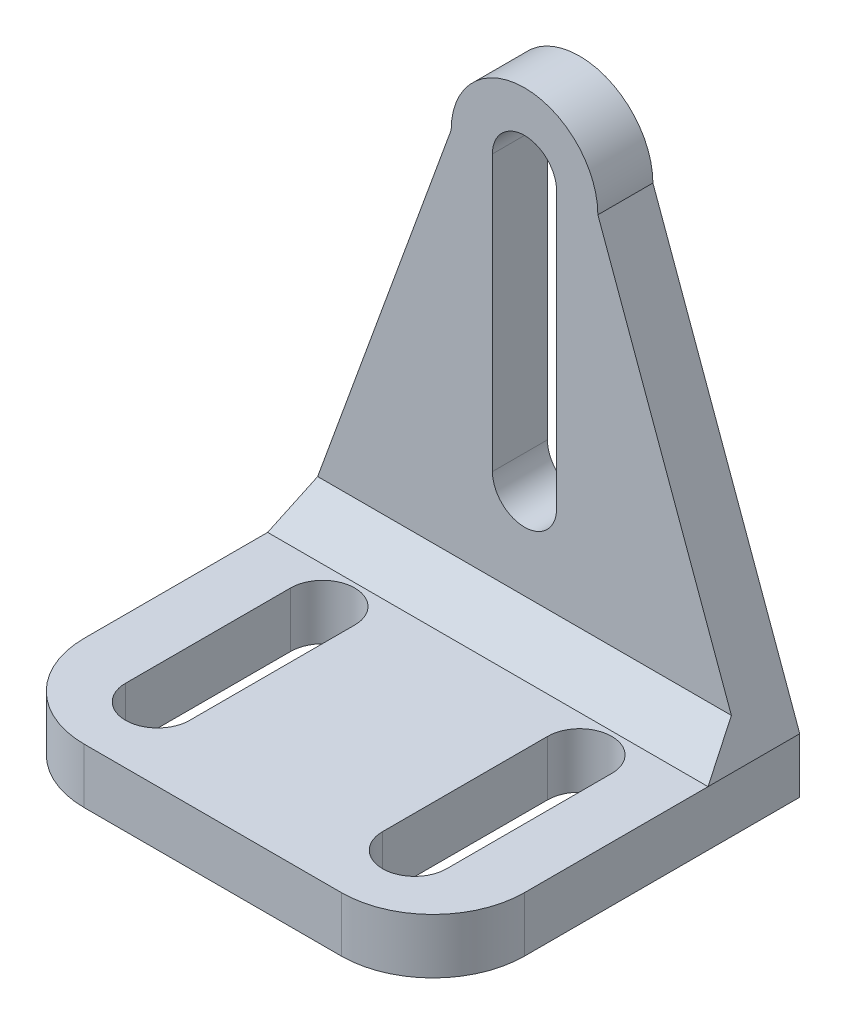
SolidWorks part; units mm, degrees
ref_plane "前视基准面" through (0, 0, 0) normal (0, 0, 1) x (1, 0, 0)
ref_plane "上视基准面" through (0, 0, 0) normal (0, 1, 0) x (1, 0, 0)
ref_plane "右视基准面" through (0, 0, 0) normal (1, 0, 0) x (0, 0, -1)
sketch "草图1" plane through (0, 0, 0) normal (0, 0, 1) x (1, 0, 0)
  line L0 (-4, 0) -> (-12.0073, -22)
  line L1 (12.0073, -22) -> (-12.0073, -22)
  line L2 (12.0073, -22) -> (4, 0)
  line L3 (0, 0) -> (0, -25) construction
  line L4 (-12.0073, -25) -> (12.0073, -25)
  line L5 (12.0073, -22) -> (12.0073, -25)
  line L6 (-12.0073, -25) -> (-12.0073, -22)
  line L7 (1.75, 0) -> (1.75, -15)
  line L8 (-1.75, 0) -> (-1.75, -15)
  circle A0 centre (0, 0) radius 1.75
  circle A1 centre (0, 0) radius 4
  circle A2 centre (0, -15) radius 1.75
  point P10 (0, -25)
  point P13 (0, -22)
  point P19 (0, 0)
  point P20 (-1.75, -8.1768)
  point P21 (1.75, -15)
  dimension "D1" = 3.5
  dimension "D2" = 8
  dimension "D6" = 3.5
  dimension "D3" = 20
  dimension "D4" = 3
  dimension "D5" = 22
  dimension "D7" = 15
extrude "凸台-拉伸1" add sketch "草图1" along normal blind 3 contours L3 A1 L0 L1 | A1 L3 L1 L2 | A0 A1 region at (-3.6673, -2.294, 0) region at (0, 3.8897, 0)
extrude "凸台-拉伸2" add sketch "草图1<3>" along normal blind 20 contours L3 L1 L6 L4 | L1 L3 L4 L5 region at (-6.0037, -23.5, 0) region at (6.0037, -23.5, 0)
sketch "草图1<3>" plane through (0, 0, 0) normal (0, 0, 1) x (1, 0, 0) same geometry as "草图1"
sketch "草图2" plane through (0, -22, 0) normal (0, 1, 0) x (1, 0, 0)
  line L0 (-7.0073, -3) -> (-7.0073, -20) construction
  line L1 (7.0073, -20) -> (7.0073, -3) construction
  line L2 (-5.2573, -7) -> (-5.2573, -16)
  line L3 (-8.7573, -7) -> (-8.7573, -16)
  line L4 (12.0073, -20) -> (12.0073, -3)
  line L5 (12.0073, -3) -> (-12.0073, -3)
  line L6 (-12.0073, -3) -> (-12.0073, -20)
  line L7 (-12.0073, -20) -> (12.0073, -20)
  line L8 (12.0073, -20) -> (12.0073, -3)
  line L9 (12.0073, -3) -> (-12.0073, -3)
  line L10 (-12.0073, -3) -> (-12.0073, -20)
  line L11 (-12.0073, -20) -> (12.0073, -20)
  line L12 (5.2573, -7) -> (5.2573, -16)
  line L13 (8.7573, -16) -> (8.7573, -7)
  circle A0 centre (-7.0073, -7) radius 1.75
  circle A1 centre (-7.0073, -16) radius 1.75
  circle A2 centre (7.0073, -7) radius 1.75
  circle A3 centre (7.0073, -16) radius 1.75
  point P24 (8.7573, -4.9402)
  point P25 (5.2573, -5.106)
  point P26 (5.2573, -12.7304)
  point P27 (-5.2573, -12.7304)
  point P28 (-8.7573, -5.4789)
  point P29 (-8.7573, -12.7304)
  dimension "D4" = 3.5
  dimension "D5" = 3.5
  dimension "D6" = 3.5
  dimension "D7" = 3.5
  dimension "D8" = 4
  dimension "D9" = 4
  dimension "D10" = 4
  dimension "D11" = 4
  dimension "D2" = 5
  dimension "D3" = 5
  dimension "D1" = 0
extrude "切除-拉伸1" cut sketch "草图2" against normal blind 15 contours A0 | A1 L2 A0 L3 | A1 | A3 | A3 L13 A2 L12 | A2 region at (-7.0073, -22, 7) region at (-7.0073, -22, 11.5) region at (-7.0073, -22, 16) region at (7.0073, -22, 11.5) region at (7.0073, -22, 7) region at (7.0073, -22, 16)
fillet "圆角1" radius 5 2 edges at (-12.0073, -23.5, 20) (12.0073, -23.5, 20)
chamfer "倒角1" distance 2 angle 45 1 edges at (0, -22, 3)
